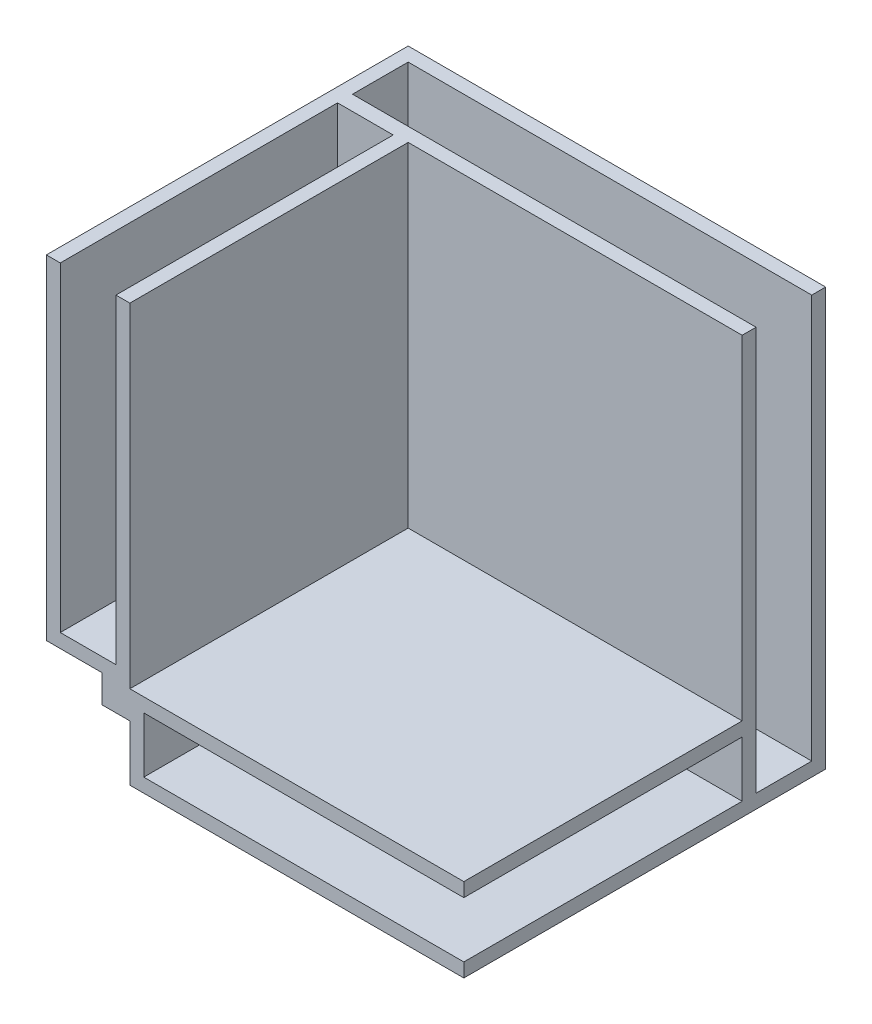
SolidWorks part; units mm, degrees
ref_plane "Front Plane" through (0, 0, 0) normal (0, 0, 1) x (1, 0, 0)
ref_plane "Top Plane" through (0, 0, 0) normal (0, 1, 0) x (1, 0, 0)
ref_plane "Right Plane" through (0, 0, 0) normal (1, 0, 0) x (0, 0, -1)
sketch "Sketch1" plane through (0, 0, 0) normal (0, 0, 1) x (1, 0, 0)
  line L1 (0, 0) -> (30, 0)
  line L2 (0, 0) -> (0, 30)
  line L3 (0, 30) -> (30, 30)
  line L4 (30, 0) -> (30, 30)
  dimension "D1" = 30
  dimension "D2" = 30
extrude "Boss-Extrude1" add sketch "Sketch1" along normal blind 6
sketch "Sketch2" plane through (0, 0, 6) normal (0, 0, 1) x (1, 0, 0)
  line L0 (0, 0) -> (30, 0) construction
  line L5 (6, 6) -> (0, 6)
  line L6 (30, 0) -> (6, 0)
  line L7 (30, 0) -> (30, 6)
  line L8 (30, 6) -> (6, 6)
  line L9 (6, 0) -> (6, 6)
  line L10 (6, 6) -> (6, 30)
  line L11 (30, 30) -> (0, 30) construction
  line L12 (6, 30) -> (0, 30)
  line L13 (0, 30) -> (0, 6)
  line L15 (5, 6) -> (6, 6)
  line L16 (5, 6) -> (5, 5)
  line L17 (5, 5) -> (6, 5)
  line L18 (6, 6) -> (6, 5)
  line M7 (0, 30) -> (0, 0)
  line M10 (30, 30) -> (0, 30)
  dimension "D1" = 6
  dimension "D2" = 6
  dimension "D3" = 1
  dimension "D4" = 1
extrude "Boss-Extrude4" add sketch "Sketch2" along normal blind 20 contours L5 L10 M10 M7 region at (3, 18, 6)
sketch "Sketch3" plane through (0, 0, 6) normal (0, 0, 1) x (1, 0, 0)
  line L1 (30, 0) -> (6, 0)
  line L2 (30, 0) -> (30, 6)
  line L3 (30, 6) -> (6, 6)
  line L4 (6, 0) -> (6, 6)
sketch "Sketch4" plane through (0, 0, 6) normal (0, 0, 1) x (1, 0, 0)
  line L1 (6, 6) -> (4, 6)
  line L2 (6, 6) -> (6, 4)
  line L3 (6, 4) -> (4, 4)
  line L4 (4, 6) -> (4, 4)
  dimension "D1" = 2
  dimension "D2" = 2
extrude "Boss-Extrude6" add sketch "Sketch4" along normal blind 20
sketch "Sketch5" plane through (0, 0, 6) normal (0, 0, 1) x (1, 0, 0)
  line L1 (6, 6) -> (30, 6)
  line L2 (6, 6) -> (6, 0)
  line L3 (6, 0) -> (30, 0)
  line L4 (30, 6) -> (30, 0)
extrude "Boss-Extrude7" add sketch "Sketch5" along normal blind 20
sketch "Sketch6" plane through (0, 0, 0) normal (0, 0, -1) x (-1, 0, 0)
  line L4 (0, 0) -> (0, 30)
  line L5 (0, 30) -> (-30, 30)
  line L6 (-30, 30) -> (-30, 0)
  line L7 (-30, 0) -> (0, 0)
  line L8 (0, 0) -> (0, 30)
  line L9 (0, 30) -> (-30, 30)
  line L10 (-30, 30) -> (-30, 0)
  line L11 (-30, 0) -> (0, 0)
  dimension "D1" = 0
shell "Shell2" thickness 1 removed face at (12, 30, 10.6667) removed face at (30, 12, 10.6667)
sketch "Sketch7" plane through (0, 5, 0) normal (0, -1, 0) x (1, 0, 0)
  line L1 (30, 5) -> (7, 5)
  line L2 (30, 5) -> (30, 6)
  line L3 (30, 6) -> (7, 6)
  line L4 (7, 5) -> (7, 6)
  dimension "D1" = 23
  dimension "D2" = 1
extrude "Boss-Extrude8" add sketch "Sketch7" along normal blind 5
sketch "Sketch8" plane through (0, 0, 6) normal (0, 0, 1) x (1, 0, 0)
  line L4 (6, 6) -> (30, 6)
  line L5 (30, 6) -> (30, 30)
  line L6 (30, 30) -> (6, 30)
  line L7 (6, 30) -> (6, 6)
  line L8 (6, 6) -> (30, 6)
  line L9 (30, 6) -> (30, 30)
  line L10 (30, 30) -> (6, 30)
  line L11 (6, 30) -> (6, 6)
  dimension "D1" = 0
sketch "Sketch9" plane through (5, 0, 0) normal (-1, 0, 0) x (0, 0, 1)
  line L1 (5, 30) -> (6.0751, 30)
  line L2 (5, 30) -> (5, 7)
  line L3 (5, 7) -> (6.0751, 7)
  line L4 (6.0751, 30) -> (6.0751, 7)
  dimension "D1" = 23
  dimension "D2" = 1.0751
extrude "Boss-Extrude9" add sketch "Sketch9" along normal blind 5
sketch "Sketch10" plane through (0, 0, 26) normal (0, 0, 1) x (1, 0, 0)
  line L0 (0, 30) -> (0, 6) construction
  line L1 (1, 7) -> (5, 7)
  line L2 (1, 7) -> (1, 30)
  line L3 (1, 30) -> (5, 30)
  line L4 (5, 7) -> (5, 30)
  line L6 (4, 6) -> (0, 6) construction
  dimension "D1" = 1
  dimension "D2" = 1
extrude "Cut-Extrude1" cut sketch "Sketch10" against normal blind 10
sketch "Sketch11" plane through (0, 0, 26) normal (0, 0, 1) x (1, 0, 0)
  line L0 (30, 0) -> (30, 6) construction
  line L1 (7, 5) -> (30, 5)
  line L2 (7, 5) -> (7, 1)
  line L3 (7, 1) -> (30, 1)
  line L4 (30, 5) -> (30, 1)
  line L5 (30, 6) -> (6, 6) construction
  line L6 (30, 0) -> (6, 0) construction
  line L7 (6, 0) -> (6, 6) construction
  point P12 (6, 3)
  dimension "D1" = 1
  dimension "D2" = 1
  dimension "D3" = 1
extrude "Cut-Extrude2" cut sketch "Sketch11" against normal blind 10
